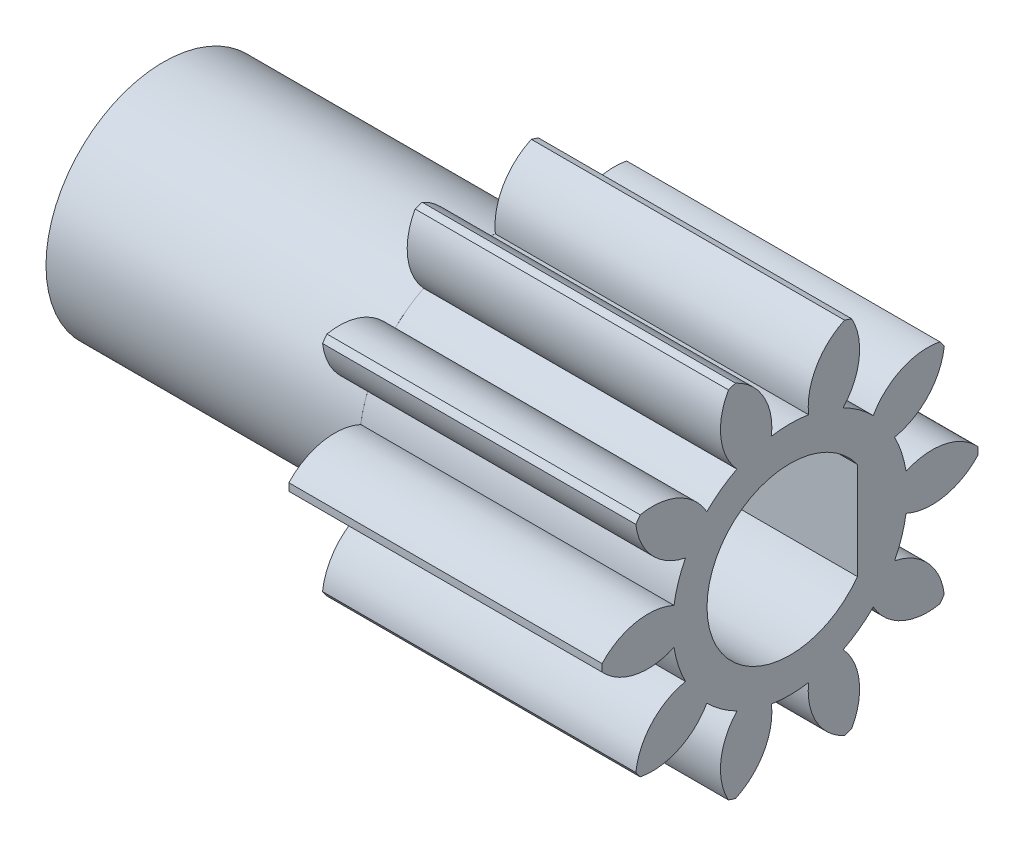
SolidWorks part; units mm, degrees
ref_plane "Plane1" through (0, 0, 0) normal (0, 0, 1) x (1, 0, 0)
ref_plane "Plane2" through (0, 0, 0) normal (0, 1, 0) x (1, 0, 0)
ref_plane "Plane3" through (0, 0, 0) normal (1, 0, 0) x (0, 0, -1)
sketch "HoldingSke" plane through (0, 0, 0) normal (0, 1, 0) x (1, 0, 0)
  line L0 (0, 0) -> (0.9848, -0.1736)
  line L1 (-15, 0) -> (100, 0) construction
  line L2 (0, 0) -> (-2.1039, 2.3779)
  line L3 (0, 0) -> (-11.863, 4.5341)
  line L4 (0, 0) -> (8.5048, 1.4996)
  line L5 (0, 0) -> (-46.8476, -17.4728)
  line L6 (0, 0) -> (-8.2896, -5.593)
  line L7 (-2.1039, 2.3779) -> (8.6586, 51.2059)
  line L8 (-76.2, 54.61) -> (-76.1, 54.61)
  line L9 (-71.009, 38.7566) -> (-53.1078, 45.2721)
  line L10 (-76.2, 71.12) -> (104.1128, 71.12)
  line L11 (0, 0) -> (-10, 0)
  line L12 (-76.2, 101.6) -> (-76.162, 101.6)
  line L13 (24.9733, 27.94) -> (52.9518, 28.4284)
  line L14 (24.9733, 27.94) -> (24.9743, 27.94)
  line L15 (24.9733, 27.94) -> (100.4006, 29.5858)
  line L16 (-63.627, -1) -> (-12.827, -1)
  circle A0 centre (0, 0) radius 0.4
  circle A1 centre (0, 0) radius 3.749
  circle A2 centre (0, 0) radius 37.5
  circle A3 centre (0, 0) radius 0.4
  dimension "MHD" = 7.498
  dimension "Hub_dia" = 75
  dimension "Bore" = 0.8
  dimension "MBD" = 0.8
  dimension "Num_teeth" = 10
  dimension "Pitch" = 1
  dimension "Overall_len" = 50
  dimension "Show_teeth" = 10
  dimension "Thickness" = 10
  dimension "OAL" = 50.0001
  dimension "T_dim" = 0.1
  dimension "Ap" = 20
  dimension "H" = 19.05
  dimension "Pitch_radius" = 180.3128
  dimension "Width" = 10
  dimension "Backlash" = 0.038
  dimension "Addendum_fac" = 1
  dimension "Dedendum_fac" = 1.25
  dimension "Clearance_fac" = 0.25
  dimension "Dedendum_add" = 0.001
  dimension "Module" = 1
sketch "BasProSke" plane through (0, 0, 0) normal (0, 1, 0) x (1, 0, 0)
  line L0 (-10, 0) -> (60, 0) construction
  line L1 (0, 0) -> (0, 6)
  line L2 (0, 0) -> (10, 0)
  line L3 (10, 0) -> (10, 6)
  line L4 (10, 6) -> (0, 6)
  dimension "Thickness" = 10
  dimension "Diameter" = 12
revolve "Base-Revolve" add sketch "BasProSke" angle 360 about L0
sketch "TooCutSke" plane through (0, 0, 0) normal (1, 0, 0) x (0, 0, -1)
  line L1 (0, 0) -> (0, 107) construction
  line L2 (0, 0) -> (-0.8485, 4.9275) construction
  line L3 (0, 0) -> (-3.0584, 9.4126) construction
  line L4 (-0.8485, 4.9275) -> (-1.5292, 4.7063) construction
  arc A0 (0.5928, 3.7018) -> (-0.5928, 3.7018) centre (0, 0) ccw
  arc A1 (1.7758, 5.7578) -> (-1.7758, 5.7578) centre (0, 0) ccw
  circle A2 centre (0, 0) radius 5 construction
  circle A3 centre (0, 0) radius 4.6985 construction
  arc A4 (-0.5928, 3.7018) -> (-1.7758, 5.7578) centre (-2.5801, 3.9267) ccw
  arc A5 (1.7758, 5.7578) -> (0.5928, 3.7018) centre (2.5801, 3.9267) ccw
  dimension "Root_dia" = 7.498
  dimension "Overcut_dia" = 12.0508
  dimension "Pitch_dia" = 10
  dimension "Base_dia" = 9.3969
  dimension "Flank_rad" = 2
  dimension "Half_ang" = 18
  dimension "Half_CT" = 0.7157
extrude "ToothCut" cut sketch "TooCutSke" along normal through all
fillet "Breaks" [suppressed] radius 0.02 tangent propagation no
fillet "RootFillets" [suppressed] radius 0.251
pattern_circular "TeethCuts" count 10 every 36 about axis through (-10, 0, 0) along (1, 0, 0) of "ToothCut", "RootFillets", "Breaks"
sketch "HubNeaOneSke" plane through (0, 0, 0) normal (-1, 0, 0) x (0, 0, 1)
  circle A0 centre (0, 0) radius 3.749
  dimension "Diameter" = 7.498
extrude "HubNearOne" [suppressed] add sketch "HubNeaOneSke" along normal blind 40.0001
sketch "HubNeaBotSke" plane through (0, 0, 0) normal (-1, 0, 0) x (0, 0, 1)
  circle A0 centre (0, 0) radius 3.749
  dimension "Diameter" = 7.498
extrude "HubNearBoth" [suppressed] add sketch "HubNeaBotSke" along normal blind 20
ref_plane "FarPln" through (10, 0, 0) normal (1, 0, 0) x (0, 0, -1)
sketch "HubFarSke" plane through (10, 0, 0) normal (1, 0, 0) x (0, 0, -1)
  circle A0 centre (0, 0) radius 3.749
  dimension "Diameter" = 7.498
extrude "HubFar" [suppressed] add sketch "HubFarSke" along normal blind 20
sketch "BorSke" plane through (0, 0, 0) normal (1, 0, 0) x (0, 0, -1)
  circle A0 centre (0, 0) radius 0.4
  dimension "Diameter" = 0.8
extrude "Bore" cut sketch "BorSke" along normal mid plane 100.0001
sketch "KeySke" plane through (0, 0, 0) normal (1, 0, 0) x (0, 0, -1)
  line L0 (-0.05, 0) -> (-0.05, 0.5)
  line L1 (-0.05, 0.5) -> (0.05, 0.5)
  line L2 (0.05, 0.5) -> (0.05, 0)
  line L3 (0, 0) -> (0, 34) construction
  line L4 (-0.05, 0) -> (0.05, 0)
  dimension "Offset" = 0.5
  dimension "Width" = 0.1
extrude "Keyway" [suppressed] cut sketch "KeySke" along normal mid plane 100.0001
pattern_circular "Keyway2" [suppressed] count 2 every 90 about axis through (-10, 0, 0) along (1, 0, 0) reverse direction yes
sketch "Croquis1" plane through (0, 0, 0) normal (-1, 0, 0) x (0, 0, 1)
  circle A0 centre (0, 0) radius 3.75
  dimension "D1" = 7.5
extrude "Saliente-Extruir1" add sketch "Croquis1" along normal blind 10
hole_wizard "Taladro de margen para M51" positions "Croquis3" profile "Croquis4" hole size "M5" standard "ISO" end condition through all
sketch "Croquis3" plane through (-10, 0, 0) normal (-1, 0, 0) x (0, 0, 1)
  point P0 (0, 0)
sketch "Croquis4" plane through (-10, 0, 0) normal (0, 1, 0) x (0, 0, 1)
  line L0 (0, 0) -> (0, 20)
  line L1 (0, 20) -> (2.65, 20)
  line L2 (2.65, 20) -> (2.65, 0)
  line L5 (2.65, 0) -> (0, 0)
  line L11 (0, -6.35) -> (0, 107.95) construction
  dimension "Diámetro de taladro hasta el siguiente" = 5.3
  dimension "Profundidad de taladro hasta el siguiente" = 20
sketch "Croquis5" plane through (10, 0, 0) normal (1, 0, 0) x (0, 0, -1)
  line L0 (-2.3506, 0) -> (2.1494, 0) construction
  line L1 (2.1494, 0) -> (2.1494, 1.55)
  line L2 (2.1494, 0) -> (2.1494, -1.55)
  circle A0 centre (0, 0) radius 2.65 construction
  arc A1 (2.1494, -1.55) -> (2.1494, 1.55) centre (0, 0) ccw
  dimension "D1" = 4.5
  dimension "D2" = 1.55
extrude "Saliente-Extruir2" add sketch "Croquis5" against normal blind 10
equation "' \"Module@HoldingSke\" = 6.35"
equation "' \"Num_teeth@HoldingSke\" = 12"
equation "' \"Ap@HoldingSke\" =  20"
equation "' \"Ap@HoldingSke\" = 20"
equation "' \"Width@HoldingSke\" = 0.5 * 25.4"
equation "' \"Hub_dia@HoldingSke\"= 1 * 25.4"
equation "' \"Hub_dia@HoldingSke\" = 1 * 25.4"
equation "' \"Overall_len@HoldingSke\" = 1.0 * 25.4"
equation "' \"Bore@HoldingSke\" = 0.75 * 25.4"
equation "' \"T_dim@HoldingSke\" = 0.1 * 25.4"
equation "' \"Width@KeySke\" = 0.25 * 25.4"
equation "' \"Show_teeth@HoldingSke\" = 13"
equation "' \"Backlash@HoldingSke\" = 0.009 * 25.4"
equation "' \"Addendum_fac@HoldingSke\" = 1.0"
equation "' \"Dedendum_fac@HoldingSke\" = 1.25"
equation "' \"Dedendum_add@HoldingSke\" = 0.00005 * 25.4"
equation "' \"Clearance_fac@HoldingSke\" = 0.25"
equation "\"Pitch@HoldingSke\" = 1 / \"Module@HoldingSke\""
equation "\"Overcut_dia@TooCutSke\" = (\"Num_teeth@HoldingSke\" + 2 * \"Addendum_fac@HoldingSke\") / \"Pitch@HoldingSke\" + 0.002 * 25.4"
equation "\"Pitch_dia@TooCutSke\" = \"Num_teeth@HoldingSke\" / \"Pitch@HoldingSke\""
equation "\"Base_dia@TooCutSke\" = \"Num_teeth@HoldingSke\" / \"Pitch@HoldingSke\" * cos((\"Ap@HoldingSke\"  * 3.14159265 / 180))"
equation "\"Root_dia@TooCutSke\" = (\"Num_teeth@HoldingSke\" + 2) / \"Pitch@HoldingSke\" - 2 * (\"Addendum_fac@HoldingSke\" + \"Dedendum_fac@HoldingSke\") / \"Pitch@HoldingSke\" - \"Dedendum_add@HoldingSke\" * 2"
equation "\"Half_ang@TooCutSke\" = 180 / \"Num_teeth@HoldingSke\""
equation "\"Half_CT@TooCutSke\" = \"Num_teeth@HoldingSke\" / \"Pitch@HoldingSke\" * sin((3.14159265 / 2 / \"Num_teeth@HoldingSke\")) / 2 - 7 * \"Backlash@HoldingSke\" / 4"
equation "\"Flank_rad@TooCutSke\" = \"Num_teeth@HoldingSke\" / \"Pitch@HoldingSke\" / 5"
equation "\"Radius@RootFillets\" = \"Clearance_fac@HoldingSke\" / \"Pitch@HoldingSke\" + \"Dedendum_add@HoldingSke\""
equation "\"Break_rad@Breaks\" = 0.02 / \"Pitch@HoldingSke\""
equation "\"Thickness@HoldingSke\" = \"Width@HoldingSke\""
equation "\"OAL@HoldingSke\" = \"Thickness@HoldingSke\""
equation "\"MHD@HoldingSke\" = (\"Num_teeth@HoldingSke\" + 2) / \"Pitch@HoldingSke\" - 2 * (\"Addendum_fac@HoldingSke\" + \"Dedendum_fac@HoldingSke\")  / \"Pitch@HoldingSke\" - \"Dedendum_add@HoldingSke\" * 2"
equation "\"MBD@HoldingSke\" = (\"Num_teeth@HoldingSke\" + 2) / \"Pitch@HoldingSke\" - 2 * (\"Addendum_fac@HoldingSke\" + \"Dedendum_fac@HoldingSke\")  / \"Pitch@HoldingSke\" - \"Dedendum_add@HoldingSke\" * 2 - 0.002 * 25.4"
equation "\"MHD@HoldingSke\" = ((sgn( \"MHD@HoldingSke\" - \"Hub_dia@HoldingSke\" )-1)*( \"MHD@HoldingSke\" - \"Hub_dia@HoldingSke\" ))/-2+ \"Hub_dia@HoldingSke\""
equation "\"MBD@HoldingSke\" = ((sgn( \"MBD@HoldingSke\" - \"Bore@HoldingSke\" )-1)*( \"MBD@HoldingSke\" - \"Bore@HoldingSke\" ))/-2+ \"Bore@HoldingSke\""
equation "\"OAL@HoldingSke\" = ((sgn( \"OAL@HoldingSke\" - \"Overall_len@HoldingSke\" )+1)*( \"OAL@HoldingSke\" - \"Overall_len@HoldingSke\" ))/2 + \"Overall_len@HoldingSke\" + 0.000002 * 25.4"
equation "\"Num_teeth@TeethCuts\" = int( \"Show_teeth@HoldingSke\" ) + 1"
equation "\"Num_teeth@TeethCuts\" = ((sgn( \"Num_teeth@TeethCuts\" - \"Num_teeth@HoldingSke\" )-1)*( \"Num_teeth@TeethCuts\" - \"Num_teeth@HoldingSke\" ))/-2+ \"Num_teeth@HoldingSke\""
equation "\"Num_teeth@TeethCuts\" = ((sgn( \"Num_teeth@TeethCuts\" - 2.0)+1)*( \"Num_teeth@TeethCuts\" - 2.0))/2 +2.0"
equation "\"Angle@TeethCuts\" = 360.0 / \"Num_teeth@HoldingSke\""
equation "\"Diameter@BasProSke\" = (\"Num_teeth@HoldingSke\" + 2 * \"Addendum_fac@HoldingSke\") / \"Pitch@HoldingSke\""
equation "\"Thickness@BasProSke\"  = \"Thickness@HoldingSke\""
equation "' \"Fillet_rad@BasProSke\" =  \"Thickness@HoldingSke\" * 0.05"
equation "' \"Fillet_rad@BasProSke\" = \"Thickness@HoldingSke\" * 0.05"
equation "\"MHD@HoldingSke\" = ((sgn( \"MHD@HoldingSke\" - \"Root_dia@TooCutSke\" )-1)*( \"MHD@HoldingSke\" - \"Root_dia@TooCutSke\" ))/-2+ \"Root_dia@TooCutSke\""
equation "\"Diameter@HubNeaOneSke\" = \"MHD@HoldingSke\""
equation "\"Length@HubNearOne\" = \"OAL@HoldingSke\" - \"Thickness@BasProSke\""
equation "\"Diameter@HubNeaBotSke\" = \"MHD@HoldingSke\""
equation "\"Length@HubNearBoth\" = ( \"OAL@HoldingSke\" - \"Thickness@BasProSke\" ) / 2.0"
equation "\"Thickness@FarPln\" = \"Thickness@BasProSke\""
equation "\"Diameter@HubFarSke\" = \"MHD@HoldingSke\""
equation "\"Length@HubFar\" = ( \"OAL@HoldingSke\" - \"Thickness@BasProSke\" ) / 2.0"
equation "\"Diameter@BorSke\" = \"MBD@HoldingSke\""
equation "\"D1@Bore\" = \"OAL@HoldingSke\" * 2.0"
equation "\"D1@Keyway\" = \"OAL@HoldingSke\" * 2.0"
equation "\"Offset@KeySke\" = \"T_dim@HoldingSke\" + \"MBD@HoldingSke\" / 2.0"
